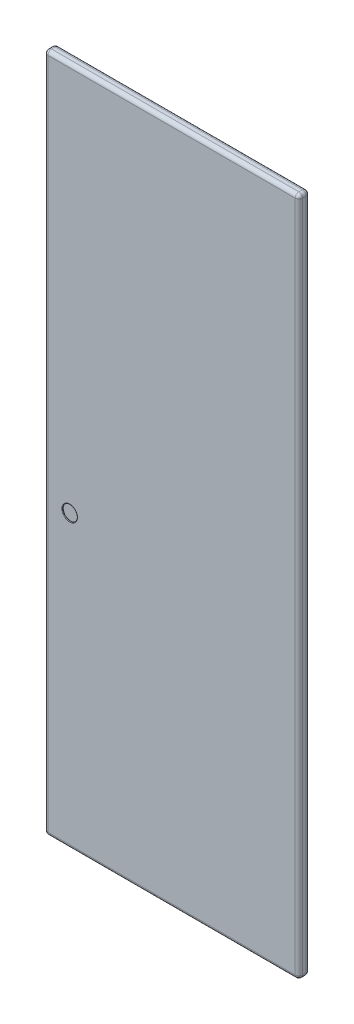
SolidWorks part; units mm, degrees
ref_plane "Front Plane" through (0, 0, 0) normal (0, 0, 1) x (1, 0, 0)
ref_plane "Top Plane" through (0, 0, 0) normal (0, 1, 0) x (1, 0, 0)
ref_plane "Right Plane" through (0, 0, 0) normal (1, 0, 0) x (0, 0, -1)
sketch "Sketch1" plane through (0, 0, 0) normal (0, 0, 1) x (1, 0, 0)
  line L1 (0, 0) -> (-700, 0)
  line L2 (0, 0) -> (0, 1870)
  line L3 (0, 1870) -> (-700, 1870)
  line L4 (-700, 0) -> (-700, 1870)
  dimension "D1" = 1870
  dimension "D2" = 700
extrude "Boss-Extrude1" add sketch "Sketch1" along normal blind 30
sketch "Sketch2" plane through (0, 0, 30) normal (0, 0, 1) x (1, 0, 0)
  line L0 (-700, 1870) -> (-700, 0) construction
  line L3 (-700, 0) -> (0, 0) construction
  circle A0 centre (-630, 800) radius 20
  point P6 (-646.315, 0)
  point P7 (-622.864, 0)
  dimension "D3" = 40
  dimension "D1" = 70
  dimension "D2" = 800
extrude "Cut-Extrude1" cut sketch "Sketch2" against normal blind 3 contours A0
sketch "Sketch3" plane through (0, 0, 27) normal (0, 0, 1) x (1, 0, 0)
  circle A0 centre (-630, 800) radius 28
  circle A1 centre (-630, 800) radius 20 construction
  circle A2 centre (-630, 800) radius 20 construction
  dimension "D1" = 8
extrude "Cut-Extrude2" cut sketch "Sketch3" against normal blind 3
fillet "Fillet1" radius 1.5 2 edges at (-610, 800, 30) (-610, 800, 27)
sketch "Sketch5" plane through (0, 0, 0) normal (0, 0, -1) x (-1, 0, 0)
  circle A0 centre (630, 800) radius 20
extrude "Cut-Extrude3" cut sketch "Sketch5" against normal blind 3
sketch "Sketch6" plane through (0, 0, 3) normal (0, 0, -1) x (-1, 0, 0)
  circle A0 centre (630, 800) radius 28
extrude "Cut-Extrude4" cut sketch "Sketch6" against normal blind 3
fillet "Fillet2" radius 1.5 2 edges at (-650, 800, 3) (-650, 800, 0)
fillet "Fillet3" radius 10 12 edges at (0, 0, 15) (-350, 0, 0) (-700, 0, 15) (-350, 0, 30) (-700, 935, 30) (-700, 935, 0) (0, 935, 0) (0, 935, 30) (0, 1870, 15) (-700, 1870, 15) (-350, 1870, 30) (-350, 1870, 0)
